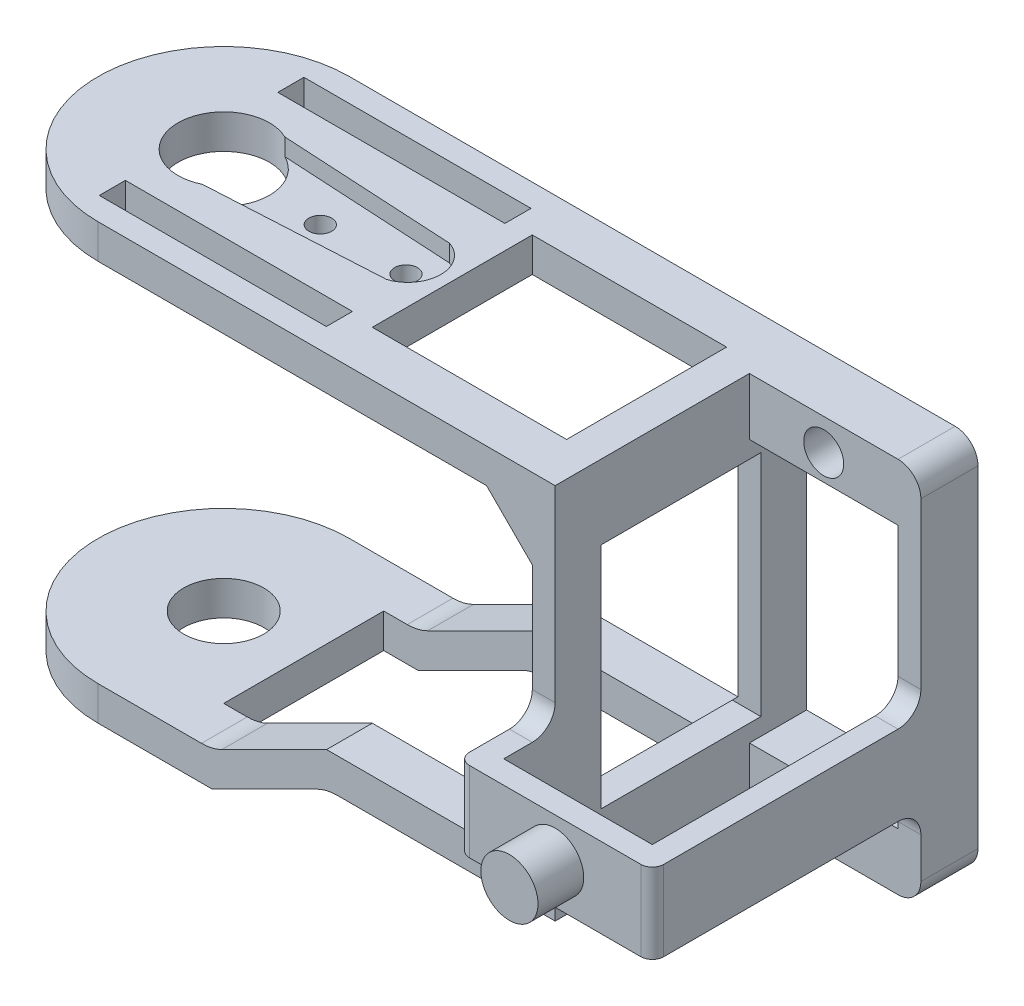
SolidWorks part; units mm, degrees
ref_plane "前视基准面" through (0, 0, 0) normal (0, 0, 1) x (1, 0, 0)
ref_plane "上视基准面" through (0, 0, 0) normal (0, 1, 0) x (1, 0, 0)
ref_plane "右视基准面" through (0, 0, 0) normal (1, 0, 0) x (0, 0, -1)
sketch "草图2" plane through (0, 0, 0) normal (0, 1, 0) x (1, 0, 0)
  line L0 (0, -11) -> (0, 11) construction
  line L1 (0, 0) -> (67.4561, 0) construction
  line L2 (0, 11) -> (40, 11)
  line L3 (40, 11) -> (40, -11)
  line L4 (40, -11) -> (0, -11)
  arc A0 (0, -11) -> (0, 11) centre (0, 0) cw
  point P5 (40, 0)
  dimension "D1" = 11
  dimension "D4" = 40
  dimension "D3" = 11
  dimension "D2" = 11
extrude "凸台-拉伸1" add sketch "草图2" along normal blind 3
sketch "草图3" plane through (0, 3, 0) normal (0, -1, 0) x (-1, 0, 0)
  line L0 (0, 0) -> (-50000, 0) construction
  line L1 (-1.7436, 3.6) -> (-1.7436, -3.6) construction
  line L2 (-17, -2.75) -> (-17, 2.75) construction
  line L3 (-1.7436, 3.6) -> (-17, 2.75)
  line L4 (-1.7436, -3.6) -> (-17, -2.75)
  arc A1 (-17, 2.75) -> (-17, -2.75) centre (-16.1094, 0) ccw
  arc A2 (-1.7436, 3.6) -> (-1.7436, -3.6) centre (0, 0) cw
  point P1 (0, 0)
  point P3 (-19, 0)
  point P6 (4, 0)
  point P9 (-17, 0)
  point P13 (-17, 0)
  point P14 (0, 0)
  dimension "D1" = 4
  dimension "D2" = 23
  dimension "D3" = 7.2
  dimension "D4" = 2
  dimension "D5" = 5.5
  dimension "D6" = 4
sketch "草图1" plane through (0, 3, 0) normal (0, 1, 0) x (1, 0, 0)
  line L0 (0, 0) -> (50000, 0) construction
  line L1 (0, -11) -> (0, 11) construction
  circle A1 centre (0, 0) radius 4
  circle A9 centre (15.95, 0) radius 1
  circle A10 centre (8.45, 0) radius 1
  point P1 (15.95, 0)
  point P8 (8.45, 0)
  point P18 (0, 0)
  dimension "D1" = 15.95
  dimension "D2" = 8
  dimension "D3" = 2
  dimension "D5" = 2
  dimension "D4" = 7.5
ref_plane "基准面1" through (0, -32, 0) normal (0, -1, 0) x (-1, 0, 0)
sketch "草图4" plane through (0, -32, 0) normal (0, -1, 0) x (-1, 0, 0)
  line L0 (0, 0.1404) -> (0, 50000.1404) construction
  line L1 (0, 0) -> (50000, 0) construction
  line L2 (0, 11) -> (-10, 11)
  line L4 (-10, 11) -> (-10, -11)
  line L5 (-10, -11) -> (0, -11)
  line L6 (0, -11) -> (-40, -11) construction
  arc A1 (0, 11) -> (0, -11) centre (0, 0) cw
  point P0 (0, 25000.1404)
  point P1 (0, 0)
  point P3 (0, 25011.1404)
  point P8 (0, -11)
  point P9 (0, 11)
  dimension "D2" = 11
  dimension "D4" = 10
  dimension "D5" = 11
  dimension "D1" = 11
  dimension "D3" = 11
extrude "凸台-拉伸2" add sketch "草图4" along normal blind 3 separate body
sketch "草图5" plane through (0, -35, 0) normal (0, -1, 0) x (-1, 0, 0)
  arc A0 (0, -11) -> (0, 11) centre (0, 0) ccw construction
  circle A1 centre (0, 0) radius 3.5
  point P0 (0, 0)
  dimension "D1" = 7
extrude "切除-拉伸3" cut sketch "草图5" against normal through all
ref_plane "基准面4" through (0, -27, 0) normal (0, -1, 0) x (-1, 0, 0)
sketch "草图8" plane through (0, -27, 0) normal (0, -1, 0) x (-1, 0, 0)
  line L1 (-20, -11) -> (-40, -11)
  line L2 (-20, -11) -> (-20, 11)
  line L3 (-20, 11) -> (-40, 11)
  line L4 (-40, -11) -> (-40, 11)
  line L5 (-20, -11) -> (-40, 11) construction
  line L6 (-20, 11) -> (-40, -11) construction
  line L7 (-40, -11) -> (-40, 11) construction
  line L8 (-40, 11) -> (0, 11) construction
  line L9 (0, -11) -> (-40, -11) construction
  point P4 (-30, 0)
  dimension "D1" = 20
extrude "凸台-拉伸4" add sketch "草图8" along normal blind 3 separate body
sketch "草图10" plane through (0, 0, 0) normal (0, 0, 1) x (1, 0, 0)
  line L0 (10, -35) -> (20, -30)
  line L2 (20, -30) -> (20, -27)
  line L3 (20, -27) -> (10, -32)
  line L4 (-17.875, -32) -> (17.875, -32) construction
  line L5 (10, -35) -> (10, -32) construction
  line L6 (10, -32) -> (10, -35)
extrude "凸台-拉伸5" add sketch "草图10" along normal up to surface and the other way up to surface up to face at (30, -28.5, 11) other way up to face at (30, -28.5, -11)
ref_plane "基准面5" through (40, 0, 0) normal (1, 0, 0) x (0, 0, -1)
sketch "草图11" plane through (40, 0, 0) normal (1, 0, 0) x (0, 0, -1)
  line L0 (-11, 3) -> (11, 3) construction
  line L1 (6, 3) -> (11, 3)
  line L2 (6, 3) -> (6, -2)
  line L3 (6, -2) -> (11, -2)
  line L4 (11, 3) -> (11, -2)
  line L5 (6, 3) -> (11, -2) construction
  line L6 (6, -2) -> (11, 3) construction
  line L9 (6, -25) -> (11, -25)
  line L17 (11, 3) -> (11, 0) construction
  line L18 (6, -25) -> (6, -30)
  line L19 (6, -30) -> (11, -30)
  line L20 (11, -25) -> (11, -30)
  line L21 (6, -25) -> (11, -30) construction
  line L22 (6, -30) -> (11, -25) construction
  point P4 (8.5, 0.5)
  point P20 (8.5, -27.5)
  dimension "D1" = 5
  dimension "D2" = 0
  dimension "D3" = 5
  dimension "D4" = 23
extrude "凸台-拉伸6" add sketch "草图11" along normal blind 15 separate body
sketch "草图13" plane through (0, 3, 0) normal (0, 1, 0) x (1, 0, 0)
  line L0 (0, -11) -> (40, -11) construction
  line L1 (40, 11) -> (38, 11)
  line L2 (40, 11) -> (40, -11)
  line L3 (40, -11) -> (38, -11)
  line L4 (38, 11) -> (38, -11)
  line L5 (40, 11) -> (38, -11) construction
  line L6 (40, -11) -> (38, 11) construction
  line L7 (40, -11) -> (40, 11) construction
  line L8 (40, 11) -> (0, 11) construction
  point P4 (39, 0)
  dimension "D1" = 2
extrude "凸台-拉伸7" add sketch "草图13" against normal up to surface (33 mm away) up to face at (30, -30, 0)
extrude "切除-拉伸7" cut sketch "草图1" against normal up to next
ref_plane "基准面7" through (0, -13.5, 0) normal (0, -1, 0) x (-1, 0, 0)
sketch "草图14" plane through (0, 0, -6) normal (0, 0, 1) x (1, 0, 0)
  line L1 (40, 3) -> (40, -2) construction
  line L2 (-2.75, -13.5) -> (2.75, -13.5) construction
  line L4 (46.5, 0.25) -> (46.5, -27.25) construction
  circle A0 centre (46.5, 0.25) radius 1.75
  circle A1 centre (46.5, -27.25) radius 1.75
  point P0 (46.5, 0.25)
  point P11 (46.5, -27.25)
  point P12 (46.5, -13.5)
  dimension "D3" = 3.5
  dimension "D4" = 3.5
  dimension "D1" = 6.5
  dimension "D2" = 27.5
sketch "草图15" plane through (0, -2, 0) normal (0, -1, 0) x (1, 0, 0)
  line L0 (55, -11) -> (40, -11) construction
  line L1 (55, -6) -> (53, -6)
  line L2 (55, -6) -> (55, -11)
  line L3 (55, -11) -> (53, -11)
  line L4 (53, -6) -> (53, -11)
  line L5 (55, -6) -> (53, -11) construction
  line L6 (55, -11) -> (53, -6) construction
  point P4 (54, -8.5)
  dimension "D1" = 2
extrude "凸台-拉伸8" add sketch "草图15" along normal up to surface (28 mm away) up to face at (38.3333, -30, -2)
extrude "切除-拉伸4" cut sketch "草图14" against normal through all
sketch "草图16" plane through (0, 0, 11) normal (0, 0, 1) x (1, 0, 0)
  line L0 (38, -27) -> (38, 0) construction
  line L1 (38, -15.45) -> (40, -15.45)
  line L2 (38, -15.45) -> (38, -22.45)
  line L3 (38, -22.45) -> (40, -22.45)
  line L4 (40, -15.45) -> (40, -22.45)
  line L5 (38, -15.45) -> (40, -22.45) construction
  line L6 (38, -22.45) -> (40, -15.45) construction
  line L9 (0, 0) -> (38, 0) construction
  line L10 (40, 3) -> (40, -30) construction
  point P4 (39, -18.95)
  dimension "D1" = 18.95
  dimension "D2" = 7
extrude "凸台-拉伸9" add sketch "草图16" along normal blind 6.5
sketch "草图17" plane through (40, 0, 0) normal (1, 0, 0) x (0, 0, -1)
  line L0 (-17.5, -22.45) -> (-11, -22.45) construction
  line L1 (-17.5, -15.45) -> (-15.5, -15.45)
  line L2 (-17.5, -15.45) -> (-17.5, -22.45)
  line L3 (-17.5, -22.45) -> (-15.5, -22.45)
  line L4 (-15.5, -15.45) -> (-15.5, -22.45)
  line L5 (-17.5, -15.45) -> (-15.5, -22.45) construction
  line L6 (-17.5, -22.45) -> (-15.5, -15.45) construction
  line L7 (-17.5, -22.45) -> (-17.5, -15.45) construction
  line L8 (-17.5, -15.45) -> (-11, -15.45) construction
  point P4 (-16.5, -18.95)
  dimension "D1" = 2
extrude "凸台-拉伸10" add sketch "草图17" along normal up to surface (15 mm away) up to face at (55, -13.5, -8.5)
sketch "草图18" plane through (0, 0, 15.5) normal (0, 0, -1) x (-1, 0, 0)
  line L0 (-55, -22.45) -> (-40, -22.45) construction
  line L1 (-55, -15.45) -> (-53, -15.45)
  line L2 (-55, -15.45) -> (-55, -22.45)
  line L3 (-55, -22.45) -> (-53, -22.45)
  line L4 (-53, -15.45) -> (-53, -22.45)
  line L5 (-55, -15.45) -> (-53, -22.45) construction
  line L6 (-55, -22.45) -> (-53, -15.45) construction
  point P4 (-54, -18.95)
  dimension "D1" = 2
extrude "凸台-拉伸11" add sketch "草图18" along normal up to surface (21.5 mm away) up to face at (48.25, 0.25, -6)
sketch "草图19" plane through (0, 0, 17.5) normal (0, 0, 1) x (1, 0, 0)
  line L0 (55, -15.45) -> (38, -15.45) construction
  line L1 (55, -15.45) -> (55, -22.45) construction
  circle A0 centre (46.5, -18.95) radius 2.5
  point P0 (46.5, -18.95)
  dimension "D3" = 5
  dimension "D1" = 3.5
  dimension "D2" = 8.5
extrude "凸台-拉伸12" add sketch "草图19" along normal blind 4
sketch "草图20" plane through (38, 0, 0) normal (-1, 0, 0) x (0, 0, 1)
  line L0 (11, -15.45) -> (11, 0) construction
  line L1 (7, -3.5) -> (-7, -3.5)
  line L2 (7, -3.5) -> (7, -23.5)
  line L3 (7, -23.5) -> (-7, -23.5)
  line L4 (-7, -3.5) -> (-7, -23.5)
  line L5 (7, -3.5) -> (-7, -23.5) construction
  line L6 (7, -23.5) -> (-7, -3.5) construction
  line L7 (-11, 0) -> (11, 0) construction
  point P4 (0, -13.5)
  dimension "D1" = 11
  dimension "D2" = 13.5
  dimension "D3" = 14
  dimension "D4" = 20
extrude "切除-拉伸5" cut sketch "草图20" against normal up to next
sketch "草图21" plane through (0, 3, 0) normal (0, 1, 0) x (1, 0, 0)
  line L0 (55, 11) -> (0, 11) construction
  line L1 (20, 7) -> (37, 7)
  line L2 (20, 7) -> (20, -7)
  line L3 (20, -7) -> (37, -7)
  line L4 (37, 7) -> (37, -7)
  line L5 (20, 7) -> (37, -7) construction
  line L6 (20, -7) -> (37, 7) construction
  line L7 (-20.9, 0) -> (20.9, 0) construction
  line L8 (-1.9358, -6.6683) -> (17.9317, -6.6683)
  line L9 (-1.9358, -6.6683) -> (-1.9358, -8.9539)
  line L10 (-1.9358, -8.9539) -> (17.9317, -8.9539)
  line L11 (17.9317, -6.6683) -> (17.9317, -8.9539)
  line L12 (-1.9358, -6.6683) -> (17.9317, -8.9539) construction
  line L13 (-1.9358, -8.9539) -> (17.9317, -6.6683) construction
  line L14 (-1.9358, 8.9539) -> (17.9317, 6.6683) construction
  line L15 (-1.9358, 6.6683) -> (17.9317, 8.9539) construction
  line L16 (17.9317, 6.6683) -> (17.9317, 8.9539)
  line L17 (-1.9358, 8.9539) -> (17.9317, 8.9539)
  line L18 (-1.9358, 6.6683) -> (-1.9358, 8.9539)
  line L19 (-1.9358, 6.6683) -> (17.9317, 6.6683)
  circle A2 centre (0, 0) radius 4 construction
  point P4 (28.5, 0)
  point P13 (7.998, -7.8111)
  point P20 (7.998, 7.8111)
  dimension "D1" = 11
  dimension "D2" = 20
  dimension "D3" = 17
  dimension "D4" = 14
extrude "切除-拉伸6" cut sketch "草图21" against normal up to next
chamfer "倒角1" distance 4 angle 45 2 edges at (38, -27, 0) (38, 0, 0)
fillet "圆角1" radius 4 2 edges at (10, -32, 0) (20, -30, 0)
fillet "圆角2" radius 2 2 edges at (55, -30, -8.5) (55, 3, -8.5)
fillet "圆角3" radius 2 4 edges at (54, -22.45, -6) (54, -15.45, -6) (39, -22.45, 11) (39, -15.45, 11)
fillet "圆角4" radius 1 2 edges at (55, -18.95, 17.5) (38, -18.95, 17.5)
extrude "切除-拉伸8" cut sketch "草图3" along normal blind 1.5
sketch "草图23" plane through (0, -27, 0) normal (0, 1, 0) x (1, 0, 0)
  line L0 (20, -7) -> (37, -7) construction
  line L1 (37, 7) -> (7, 7)
  line L2 (37, 7) -> (37, -7)
  line L3 (37, -7) -> (7, -7)
  line L4 (7, 7) -> (7, -7)
  line L5 (37, 7) -> (7, -7) construction
  line L6 (37, -7) -> (7, 7) construction
  line L7 (37, 7) -> (20, 7) construction
  line L8 (37, -7) -> (37, 7) construction
  point P4 (22, 0)
  dimension "D1" = 30
extrude "切除-拉伸10" cut sketch "草图23" against normal up to next
